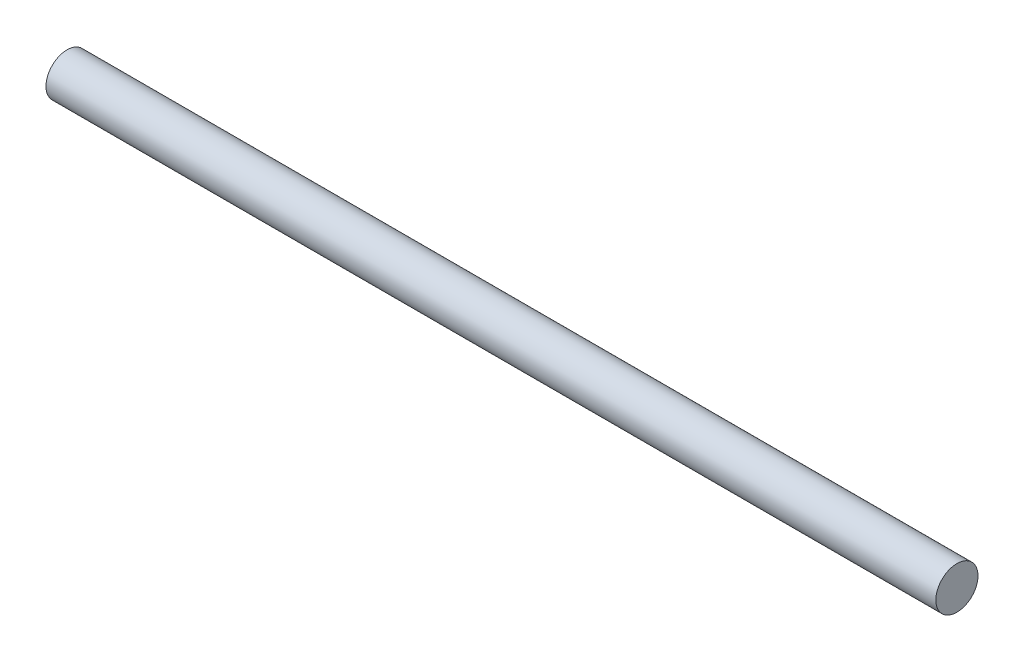
SolidWorks part; units mm, degrees
material "ABS"
ref_plane "Front Plane" through (0, 0, 0) normal (0, 0, 1) x (1, 0, 0)
ref_plane "Top Plane" through (0, 0, 0) normal (0, 1, 0) x (1, 0, 0)
ref_plane "Right Plane" through (0, 0, 0) normal (1, 0, 0) x (0, 0, -1)
sketch "Sketch2" plane through (0, 0, 0) normal (1, 0, 0) x (0, 0, -1)
  circle A0 centre (0, 0) radius 5
  dimension "D1" = 10
extrude "Boss-Extrude1" add sketch "Sketch2" along normal mid plane 211
